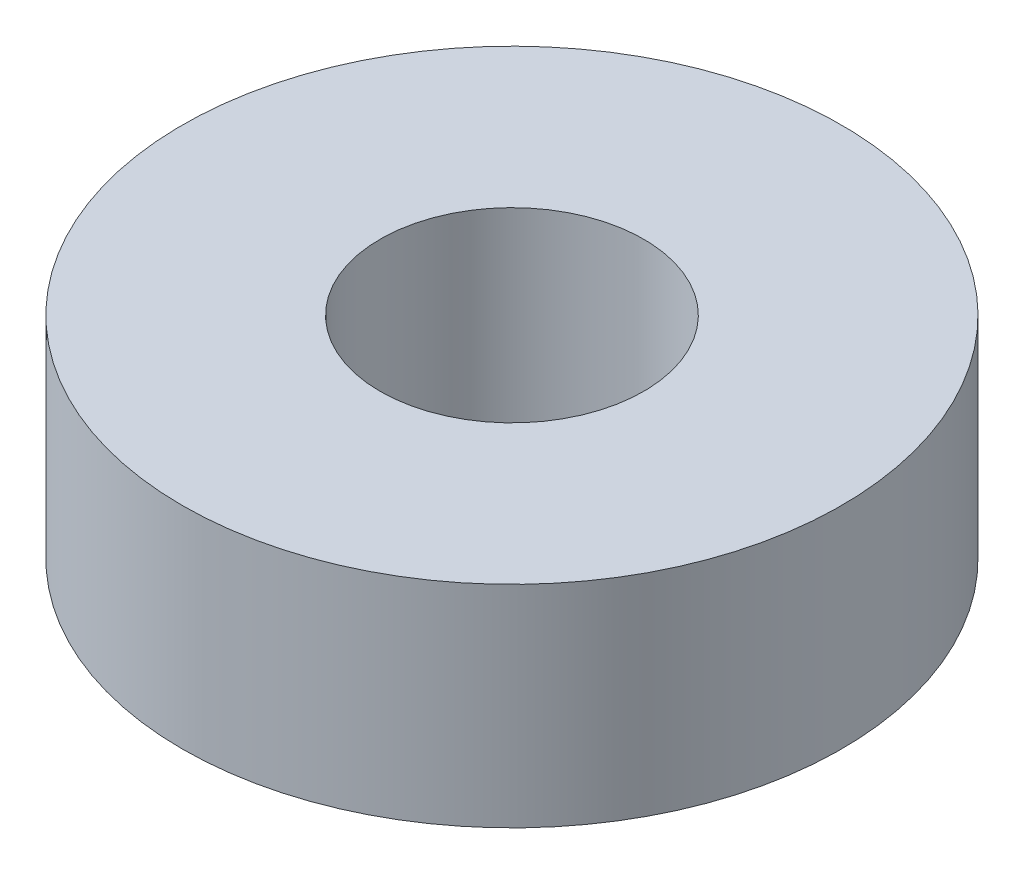
SolidWorks part; units mm, degrees
ref_plane "Front Plane" through (0, 0, 0) normal (0, 0, 1) x (1, 0, 0)
ref_plane "Top Plane" through (0, 0, 0) normal (0, 1, 0) x (1, 0, 0)
ref_plane "Right Plane" through (0, 0, 0) normal (1, 0, 0) x (0, 0, -1)
sketch "Sketch1" plane through (0, 0, 0) normal (0, 1, 0) x (1, 0, 0)
  circle A0 centre (0, 0) radius 25
  dimension "FLANGE_OD" = 50
extrude "Boss-Extrude1" add sketch "Sketch1" along normal blind 16
sketch "Sketch2" plane through (0, 0, 0) normal (0, 1, 0) x (1, 0, 0)
  circle A0 centre (0, 0) radius 10
  dimension "BORE_D" = 20
extrude "Cut-Extrude1" cut sketch "Sketch2" along normal through all
sketch "Sketch3" plane through (0, 16, 0) normal (0, 1, 0) x (1, 0, 0)
  circle A0 centre (0, 0) radius 7.1599 construction
  circle A1 centre (-7.1599, 0) radius 2.0493
  dimension "BOLT_D" = 4.0986
  dimension "BOLT_PCD" = 14.3199
extrude "Cut-Extrude2" cut sketch "Sketch3" against normal blind 12.3443 rebuild error yes
pattern_circular "CirPattern1" count 6 over 360 rebuild error yes
